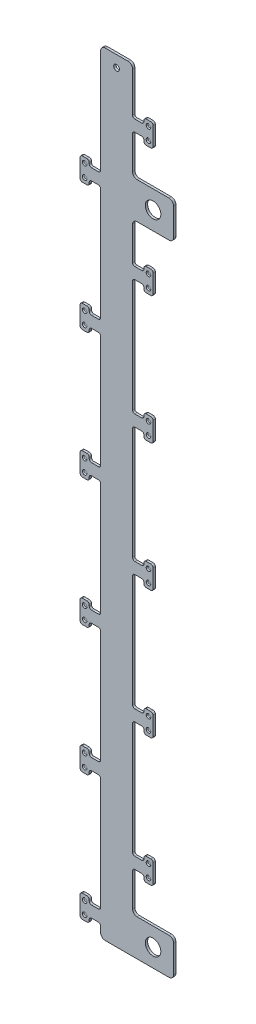
SolidWorks part; units mm, degrees
ref_plane "Plan de face" through (0, 0, 0) normal (0, 0, 1) x (1, 0, 0)
ref_plane "Plan de dessus" through (0, 0, 0) normal (0, 1, 0) x (1, 0, 0)
ref_plane "Plan de droite" through (0, 0, 0) normal (1, 0, 0) x (0, 0, -1)
sketch "Esquisse1" plane through (0, 0, 0) normal (0, 0, 1) x (1, 0, 0)
  line L1 (-3.5, -84.75) -> (3.5, -84.75)
  line L2 (-3.5, -84.75) -> (-3.5, 84.75)
  line L3 (-3.5, 84.75) -> (3.5, 84.75)
  line L4 (3.5, -84.75) -> (3.5, 84.75)
  line L5 (-3.5, -84.75) -> (3.5, 84.75) construction
  line L6 (-3.5, 84.75) -> (3.5, -84.75) construction
  point P0 (0, 0)
  dimension "D1" = 169.5
  dimension "D2" = 7
extrude "Boss.-Extru.1" add sketch "Esquisse1" along normal blind 0.51
sketch "Esquisse2" plane through (0, 0, 0.51) normal (0, 0, 1) x (1, 0, 0)
  line L0 (3.5, 84.75) -> (-3.5, 84.75) construction
  circle A0 centre (0, 82.25) radius 0.625
  dimension "D1" = 1.25
  dimension "D2" = 2.5
extrude "Enlèv. mat.-Extru.1" cut sketch "Esquisse2" against normal through all
sketch "Esquisse4" plane through (0, 0, 0.51) normal (0, 0, 1) x (1, 0, 0)
  line L0 (3.5, -84.75) -> (3.5, 84.75) construction
  line L1 (3.5, 74.5) -> (6, 74.5)
  line L2 (3.5, 74.5) -> (3.5, 72)
  line L3 (3.5, 72) -> (6, 72)
  line L5 (6, 72) -> (6, 70.75)
  line L6 (6, 75.75) -> (8, 75.75)
  line L7 (6, 75.75) -> (6, 74.5)
  line L8 (6, 70.75) -> (8, 70.75)
  line L9 (8, 75.75) -> (8, 70.75)
  line L10 (3.5, 84.75) -> (-3.5, 84.75) construction
  line L11 (-3.5, 84.75) -> (-3.5, -84.75) construction
  line L12 (-3.5, 58) -> (-6, 58)
  line L13 (-3.5, 58) -> (-3.5, 60.5)
  line L14 (-3.5, 60.5) -> (-6, 60.5)
  line L16 (-6, 60.5) -> (-6, 61.75)
  line L17 (-6, 56.75) -> (-8, 56.75)
  line L18 (-6, 56.75) -> (-6, 58)
  line L19 (-6, 61.75) -> (-8, 61.75)
  line L20 (-8, 56.75) -> (-8, 61.75)
  point P10 (8, 73.25)
  point P11 (3.5, 73.25)
  point P24 (-3.5, 59.25)
  point P25 (-8, 59.25)
  dimension "D1" = 2.5
  dimension "D2" = 2.5
  dimension "D3" = 2
  dimension "D4" = 5
  dimension "D5" = 10.25
  dimension "D6" = 2.5
  dimension "D7" = 2.5
  dimension "D8" = 5
  dimension "D9" = 2
  dimension "D10" = 23
extrude "Boss.-Extru.2" add sketch "Esquisse4" against normal up to surface (0.51 mm away) up to face at (0.625, 82.25, 0)
fillet "Congé1" radius 0.5 16 edges at (6, 72, 0.255) (8, 70.75, 0.255) (6, 70.75, 0.255) (3.5, 72, 0.255) (8, 75.75, 0.255) (6, 75.75, 0.255) (6, 74.5, 0.255) (3.5, 74.5, 0.255) (-3.5, 58, 0.255) (-8, 56.75, 0.255) (-6, 58, 0.255) (-3.5, 60.5, 0.255) (-6, 56.75, 0.255) (-8, 61.75, 0.255) (-6, 61.75, 0.255) (-6, 60.5, 0.255)
sketch "Esquisse5" plane through (0, 0, 0) normal (0, 0, -1) x (-1, 0, 0)
  line L0 (-7, 74.6) -> (-7, 71.9) construction
  line L1 (-8, 71.25) -> (-8, 75.25) construction
  line L2 (-7.5, 75.75) -> (-6.5, 75.75) construction
  line L3 (7, 60.6) -> (7, 57.9) construction
  line L4 (6.5, 61.75) -> (7.5, 61.75) construction
  line L5 (8, 61.25) -> (8, 57.25) construction
  circle A0 centre (-7, 74.6) radius 0.5
  circle A1 centre (-7, 71.9) radius 0.5
  circle A2 centre (7, 60.6) radius 0.5
  circle A3 centre (7, 57.9) radius 0.5
  point P4 (-7, 73.25)
  point P7 (-8, 73.25)
  point P10 (-7, 75.75)
  point P17 (7, 61.75)
  point P18 (7, 59.25)
  point P21 (8, 59.25)
  dimension "D1" = 1
  dimension "D4" = 1
  dimension "D2" = 2.7
  dimension "D3" = 2.7
extrude "Boss.-Extru.3" add sketch "Esquisse5" along normal blind 0.2
sketch "Esquisse6" plane through (0, 0, 0.51) normal (0, 0, 1) x (1, 0, 0)
  circle A0 centre (7, 71.9) radius 0.5 construction
  circle A1 centre (7, 74.6) radius 0.5 construction
  circle A2 centre (7, 71.9) radius 0.5
  circle A3 centre (7, 74.6) radius 0.5
  circle A4 centre (-7, 57.9) radius 0.5 construction
  circle A5 centre (-7, 60.6) radius 0.5 construction
  circle A6 centre (-7, 57.9) radius 0.5
  circle A7 centre (-7, 60.6) radius 0.5
extrude "Enlèv. mat.-Extru.2" cut sketch "Esquisse6" against normal blind 0.2
fillet "Congé3" radius 0.1 8 edges at (6.5, 74.6, -0.2) (6.5, 71.9, -0.2) (6.5, 71.9, 0) (6.5, 74.6, 0) (-7.5, 60.6, 0) (-7.5, 60.6, -0.2) (-7.5, 57.9, 0) (-7.5, 57.9, -0.2)
fillet "Congé4" radius 0.2 4 edges at (7.5, 71.9, 0.31) (7.5, 74.6, 0.31) (-6.5, 57.9, 0.31) (-6.5, 60.6, 0.31)
pattern_linear "Répétition linéaire8" count 11 spacing 14 along (0, -1, 0) skipping (1, 0), (3, 0), (5, 0), (7, 0), (9, 0) of "Congé4", "Congé3", "Boss.-Extru.3", "Congé1", "Enlèv. mat.-Extru.2", "Boss.-Extru.2"
sketch "Esquisse7" plane through (0, 0, 0.51) normal (0, 0, 1) x (1, 0, 0)
  line L0 (3.5, 47) -> (3.5, 71.5) construction
  line L1 (3.5, 63.25) -> (12.5, 63.25)
  line L2 (3.5, 63.25) -> (3.5, 55.25)
  line L3 (3.5, 55.25) -> (12.5, 55.25)
  line L4 (12.5, 63.25) -> (12.5, 55.25)
  line L5 (-8, 61.25) -> (-8, 57.25) construction
  circle A0 centre (8, 59.25) radius 1.7
  point P6 (3.5, 59.25)
  point P9 (-8, 59.25)
  point P12 (8, 63.25)
  point P13 (12.5, 59.25)
  dimension "D3" = 3.4
  dimension "D1" = 9
  dimension "D2" = 8
extrude "Boss.-Extru.4" add sketch "Esquisse7" against normal up to surface (0.51 mm away) up to face at (-7.6, -79.4, 0)
pattern_linear "Répétition linéaire9" count 11 spacing 14 along (0, -1, 0) skipping (1, 0), (2, 0), (3, 0), (4, 0), (5, 0), (6, 0), (7, 0), (8, 0), (9, 0) of "Boss.-Extru.4"
fillet "Congé5" radius 1 10 edges at (3.5, 55.25, 0.255) (12.5, 55.25, 0.255) (12.5, 63.25, 0.255) (3.5, 63.25, 0.255) (3.5, -76.75, 0.255) (12.5, -84.75, 0.255) (12.5, -76.75, 0.255) (-3.5, 84.75, 0.255) (3.5, 84.75, 0.255) (-3.5, -84.75, 0.255)
